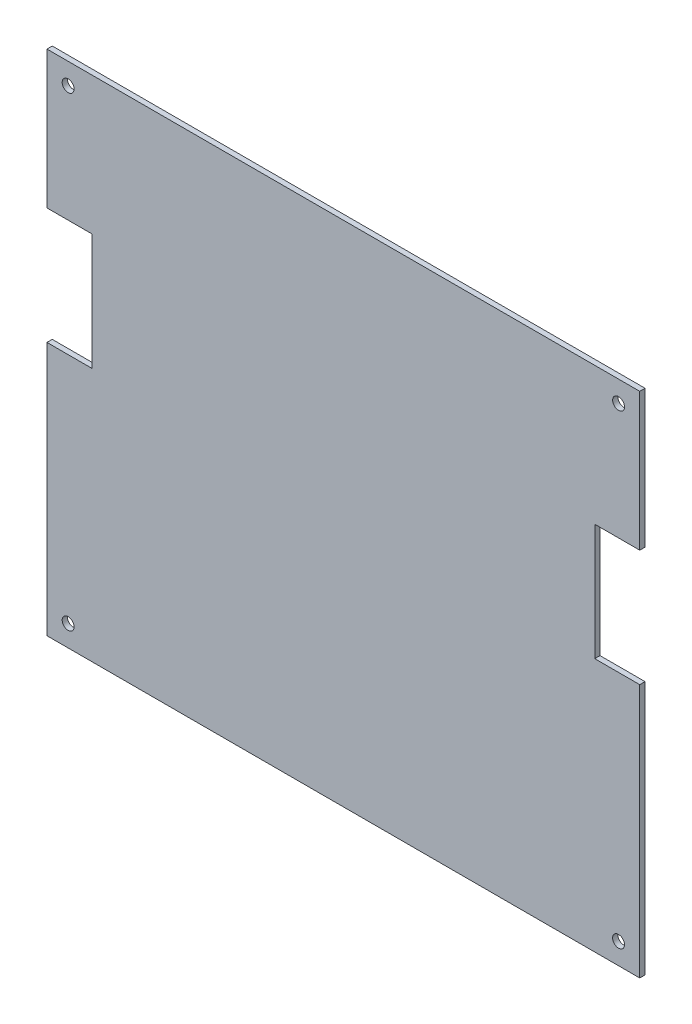
SolidWorks part; units mm, degrees
material "Acrylic (Medium-high impact)"
ref_plane "Front Plane" through (0, 0, 0) normal (0, 0, 1) x (1, 0, 0)
ref_plane "Top Plane" through (0, 0, 0) normal (0, 1, 0) x (1, 0, 0)
ref_plane "Right Plane" through (0, 0, 0) normal (1, 0, 0) x (0, 0, -1)
sketch "Sketch1" plane through (0, 0, 0) normal (0, 0, 1) x (1, 0, 0)
  line L1 (0, 0) -> (355.6, 0)
  line L2 (0, 0) -> (0, -304.8)
  line L3 (0, -304.8) -> (355.6, -304.8)
  line L4 (355.6, 0) -> (355.6, -304.8)
  dimension "D1" = 355.6
  dimension "D2" = 304.8
extrude "Boss-Extrude1" add sketch "Sketch1" along normal blind 3.175
sketch "Sketch2" plane through (0, 0, 3.175) normal (0, 0, 1) x (1, 0, 0)
  line L0 (177.8, 0) -> (177.8, -304.8) construction
  line L1 (355.6, 0) -> (0, 0) construction
  line L2 (0, -304.8) -> (355.6, -304.8) construction
  line L3 (0, -152.4) -> (355.6, -152.4) construction
  line L4 (0, 0) -> (0, -304.8) construction
  line L5 (355.6, -304.8) -> (355.6, 0) construction
  point P0 (12.7, -12.7)
  point P13 (342.9, -12.7)
  point P15 (342.9, -292.1)
  point P16 (12.7, -292.1)
  dimension "D1" = 12.7
  dimension "D2" = 12.7
hole_wizard "1/4 Clearance Hole1" positions "Sketch2" profile "Sketch3" hole size "1/4" standard "ANSI Inch" end condition up to next
sketch "Sketch3" plane through (12.7, -12.7, 3.175) normal (1, 0, 0) x (0, -1, 0)
  line L0 (0, 0) -> (0, 3.175)
  line L1 (0, 3.175) -> (3.5712, 3.175)
  line L2 (3.5712, 3.175) -> (3.5712, 0)
  line L5 (3.5712, 0) -> (0, 0)
  line L11 (0, -6.35) -> (0, 107.95) construction
  dimension "Thru Hole Dia." = 7.1425
  dimension "Thru Hole Depth" = 3.175
sketch "Sketch4" plane through (0, 0, 3.175) normal (0, 0, 1) x (1, 0, 0)
  line L0 (177.8, 0) -> (177.8, -304.8) construction
  line L1 (355.6, 0) -> (0, 0) construction
  line L2 (0, -304.8) -> (355.6, -304.8) construction
  line L3 (0, -152.4) -> (355.6, -152.4) construction
  line L4 (0, 0) -> (0, -304.8) construction
  line L6 (328.6125, -152.4) -> (355.6, -152.4)
  line L7 (26.9875, -152.4) -> (0, -152.4)
  line L8 (26.9875, -152.4) -> (26.9875, -82.55)
  line L9 (26.9875, -82.55) -> (0, -82.55)
  line L10 (0, -152.4) -> (0, -82.55)
  line L11 (355.6, -152.4) -> (355.6, -82.55)
  line L12 (328.6125, -152.4) -> (328.6125, -82.55)
  line L13 (328.6125, -82.55) -> (355.6, -82.55)
  point P10 (0, 0)
  point P18 (0, 0)
  dimension "D1" = 69.85
  dimension "D2" = 26.9875
extrude "Cut-Extrude1" cut sketch "Sketch4" against normal up to next
